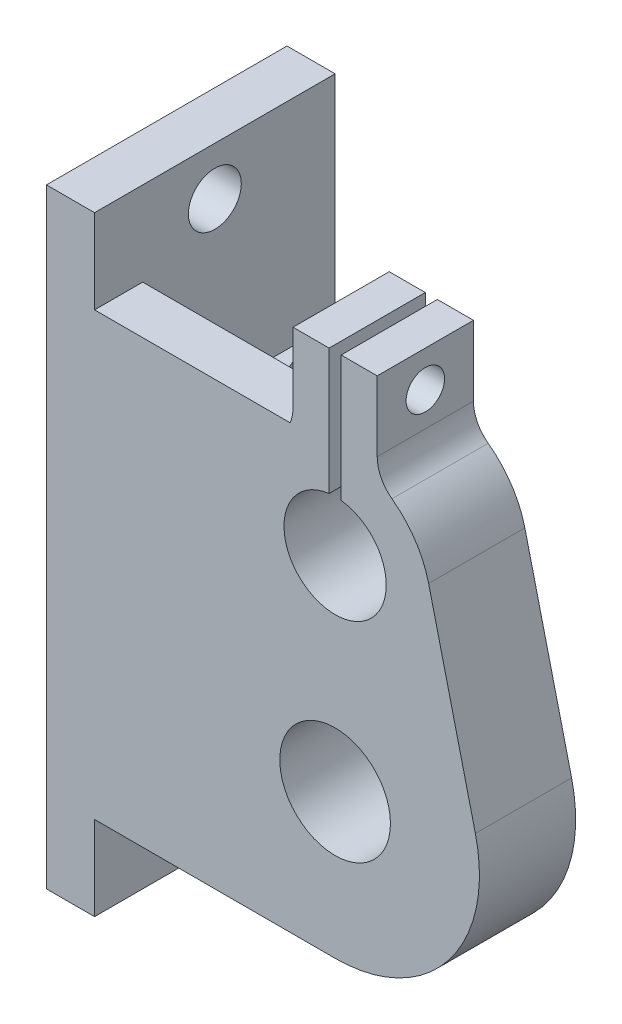
SolidWorks part; units mm, degrees
ref_plane "前视基准面" through (0, 0, 0) normal (0, 0, 1) x (1, 0, 0)
ref_plane "上视基准面" through (0, 0, 0) normal (0, 1, 0) x (1, 0, 0)
ref_plane "右视基准面" through (0, 0, 0) normal (1, 0, 0) x (0, 0, -1)
sketch "草图1" plane through (0, 0, 0) normal (0, 0, 1) x (1, 0, 0)
  line L0 (-1000, 0) -> (49000, 0) construction
  line L1 (-999.6726, 42) -> (49000.3274, 42) construction
  line L2 (0, -1000) -> (0, 49000) construction
  line L3 (48, -1000) -> (48, 49000) construction
  line L4 (16.2246, 39.8824) -> (12.3369, 23.8235)
  line L5 (31.7754, 39.8824) -> (35.6631, 23.8235)
  line L6 (0, 52.6937) -> (0, 2)
  line L7 (0, 2) -> (4, 2)
  line L8 (4, 2) -> (4, 9)
  line L9 (4, 9) -> (44, 9)
  line L10 (0, 52.6937) -> (4, 52.6937)
  line L11 (4, 45.6937) -> (21.8077, 45.6937)
  line L12 (4, 45.6937) -> (4, 52.6937)
  line L13 (24, -979.7827) -> (24, 49020.2173) construction
  line L14 (20.5, 52.6937) -> (20.5, 46.8741)
  line L15 (20.5, 52.6937) -> (23.5, 52.6937)
  line L16 (23.5, 52.6937) -> (23.5, 42.2205)
  line L17 (24.5, 52.6937) -> (24.5, 42.2205)
  line L18 (27.5, 52.6937) -> (24.5, 52.6937)
  line L19 (27.5, 52.6937) -> (27.5, 46.8741)
  line L20 (48, 2) -> (44, 2)
  line L21 (44, 45.6937) -> (26.1923, 45.6937)
  line L22 (44, 45.6937) -> (44, 52.6937)
  line L23 (48, 52.6937) -> (48, 2)
  line L24 (48, 52.6937) -> (44, 52.6937)
  line L25 (44, 2) -> (44, 9)
  line L26 (4, 45.6937) -> (4, 9)
  line L27 (44, 45.6937) -> (44, 9)
  circle A0 centre (24, 21) radius 11.5 construction
  circle A1 centre (24, 38) radius 4 construction
  circle A2 centre (24, 21) radius 4.6
  arc A3 (23.5, 42.2205) -> (24.5, 42.2205) centre (24, 38) ccw
  arc A4 (31.7754, 39.8824) -> (28.7273, 44.4539) centre (24, 38) ccw
  arc A5 (12.3369, 23.8235) -> (35.6631, 23.8235) centre (24, 21) ccw
  arc A6 (19.2727, 44.4539) -> (16.2246, 39.8824) centre (24, 38) ccw
  arc A7 (20.5, 46.8741) -> (19.2727, 44.4539) centre (17.5, 46.8741) cw
  arc A8 (27.5, 46.8741) -> (28.7273, 44.4539) centre (30.5, 46.8741) ccw
  point P39 (24, 9)
  point P45 (20.5, 45.1937)
  point P48 (27.5, 45.1937)
  dimension "D3" = 8.5
  dimension "D4" = 9.2
  dimension "D5" = 16
  dimension "D6" = 24
  dimension "D13" = 3
  dimension "D1" = 48
  dimension "D2" = 42
  dimension "D7" = 4
  dimension "D8" = 3
  dimension "D9" = 0.5
  dimension "D10" = 7.5
  dimension "D11" = 7
  dimension "D12" = 7
extrude "凸台-拉伸1" add sketch "草图1" along normal blind 4 contours A6 L11 L12 L10 L6 L7 L8 L9 A5 L4 | L14 A6 L4 A5 L5 A4 L19 L18 L17 A3 L16 L15 A2 | L26 L12 L10 L6 L7 L8 region at (24, 27.4704, 0) region at (9.6395, 28.1152, 0) region at (2, 27.3469, 0)
extrude "凸台-拉伸2" add sketch "草图1<4>" against normal blind 4 contours L14 A6 L4 A5 L5 A4 L19 L18 L17 A3 L16 L15 A2 | L26 L12 L10 L6 L7 L8 region at (24, 27.4704, 0) region at (2, 27.3469, 0)
sketch "草图1<4>" plane through (0, 0, 0) normal (0, 0, 1) x (1, 0, 0) same geometry as "草图1"
extrude "凸台-拉伸3" add sketch "草图1<5>" against normal blind 12 from surface contours L26 L12 L10 L6 L7 L8 region at (2, 27.3469, 0) starting at face at (2, 27.3469, -4)
sketch "草图1<5>" plane through (0, 0, 0) normal (0, 0, 1) x (1, 0, 0) same geometry as "草图1"
sketch "草图4" plane through (4, 0, 0) normal (1, 0, 0) x (0, 0, -1)
  line L2 (-4, 2) -> (16, 2) construction
  line L3 (16, 27.3469) -> (-4, 27.3469) construction
  line L4 (16, 52.6937) -> (16, 2) construction
  line L5 (-4, 39.8824) -> (-4, 23.8235) construction
  circle A0 centre (0, 49.6937) radius 1.6
  circle A1 centre (6, 6) radius 2.2
  circle A2 centre (6, 48.6937) radius 2.2
  circle A3 centre (6, 6) radius 4 construction
  circle A4 centre (6, 48.6937) radius 4 construction
  circle A5 centre (6, 6) radius 1.5 construction
  circle A6 centre (6, 48.6937) radius 1.5 construction
  dimension "D1" = 3.2
  dimension "D4" = 4.4
  dimension "D6" = 8
  dimension "D5" = 3
  dimension "D2" = 3
  dimension "D3" = 6
extrude "切除-拉伸2" cut sketch "草图4" against normal blind 12 contours A2 | A1 region at (4, 6, -6) region at (4, 48.6937, -6)
extrude "切除-拉伸3" cut sketch "草图4<3>" along normal through all contours A0 region at (4, 49.6937, 0)
sketch "草图4<3>" plane through (4, 0, 0) normal (1, 0, 0) x (0, 0, -1) same geometry as "草图4"
ref_plane "基准面1" through (0, 19, 0) normal (0, -1, 0) x (-1, 0, 0)
ref_plane "基准面2" through (0, 32.3469, 0) normal (0, -1, 0) x (-1, 0, 0)
sketch "草图6" plane through (0, 19, 0) normal (0, -1, 0) x (-1, 0, 0)
  line L0 (-4, 14) -> (-10, 0)
  line L1 (-4, -4) -> (-4, 16) construction
  dimension "D1" = 14
  dimension "D2" = 10
rib "筋6" sketch "草图6" sketch "草图6" thickness 5 extrusion direction parallel to sketch draft on no parameters "D1"=5
sketch "草图8" plane through (0, 32.3469, 0) normal (0, -1, 0) x (-1, 0, 0)
  line L0 (-4, 14) -> (-10, 0) construction
  line L1 (-4, 14) -> (-10, 0)
rib "筋7" sketch "草图8" sketch "草图8" thickness 5 extrusion direction parallel to sketch draft on no parameters "D1"=5
